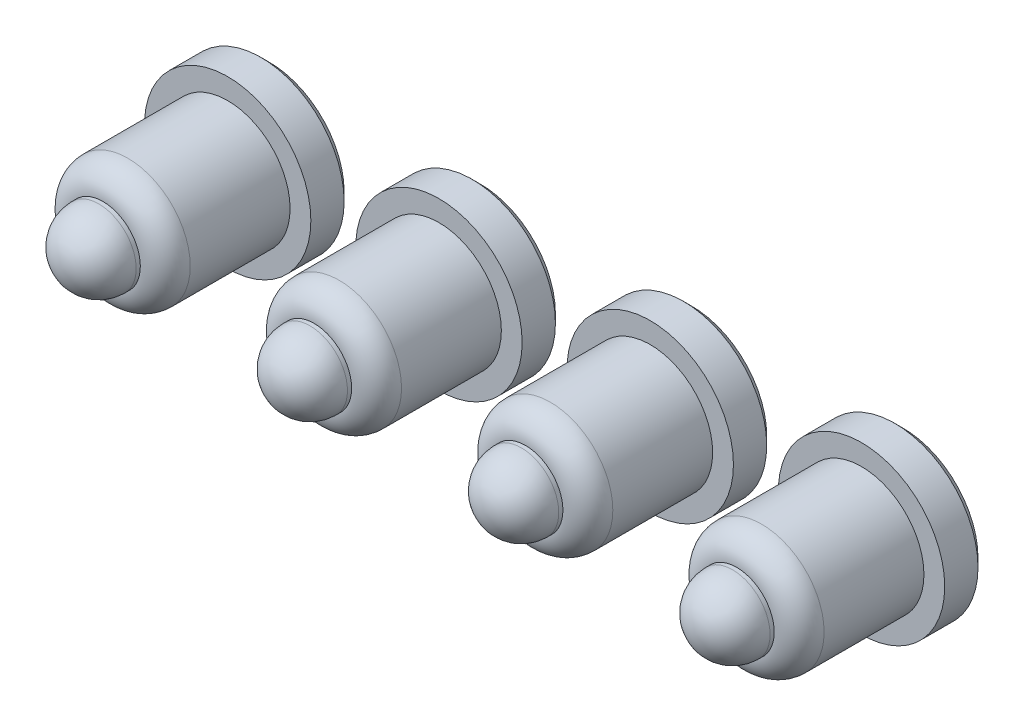
SolidWorks part; units mm, degrees
material "黄铜"
ref_plane "前视基准面" through (0, 0, 0) normal (0, 0, 1) x (1, 0, 0)
ref_plane "上视基准面" through (0, 0, 0) normal (0, 1, 0) x (1, 0, 0)
ref_plane "右视基准面" through (0, 0, 0) normal (1, 0, 0) x (0, 0, -1)
sketch "草图1" plane through (0, 0, 0) normal (0, 0, 1) x (1, 0, 0)
  circle A0 centre (0, 0) radius 0.75
  circle A1 centre (2.54, 0) radius 0.75
  circle A2 centre (5.08, 0) radius 0.75
  circle A3 centre (7.62, 0) radius 0.75
  dimension "D1" = 4
extrude "凸台-拉伸1" add sketch "草图1" along normal blind 1.5
sketch "草图2" plane through (0, 0, 0) normal (0, 0, 1) x (1, 0, 0)
  circle A0 centre (0, 0) radius 1
  circle A1 centre (2.54, 0) radius 1
  circle A2 centre (5.08, 0) radius 1
  circle A3 centre (7.62, 0) radius 1
  dimension "D1" = 4
extrude "凸台-拉伸2" add sketch "草图2" against normal blind 0.5
sketch "草图3" plane through (0, 0, 1.5) normal (0, 0, 1) x (1, 0, 0)
  circle A0 centre (0, 0) radius 0.45
  circle A1 centre (2.54, 0) radius 0.45
  circle A2 centre (5.08, 0) radius 0.45
  circle A3 centre (7.62, 0) radius 0.45
  dimension "D1" = 4
extrude "凸台-拉伸3" add sketch "草图3" along normal blind 0.5
pattern_linear "阵列(线性)6" count 4 spacing 2.54 along (0, 1, 0) of "凸台-拉伸1", "凸台-拉伸2", "凸台-拉伸3"
fillet "圆角1" radius 0.3 1 edges at (0.75, 0, 1.5)
fillet "圆角2" radius 0.45 1 edges at (0.45, 0, 2)
chamfer "倒角1" distance 0.1 angle 45 1 edges at (3.54, 0, -0.5)
chamfer "倒角2" distance 0.1 angle 45 1 edges at (1, 0, -0.5)
chamfer "倒角3" distance 0.1 angle 45 1 edges at (6.08, 0, -0.5)
chamfer "倒角4" distance 0.1 angle 45 1 edges at (8.62, 0, -0.5)
fillet "圆角3" radius 0.3 1 edges at (3.29, 0, 1.5)
fillet "圆角4" radius 0.3 1 edges at (5.83, 0, 1.5)
fillet "圆角5" radius 0.3 1 edges at (8.37, 0, 1.5)
fillet "圆角6" radius 0.45 1 edges at (2.99, 0, 2)
fillet "圆角7" radius 0.45 1 edges at (5.53, 0, 2)
fillet "圆角8" radius 0.45 1 edges at (8.07, 0, 2)
